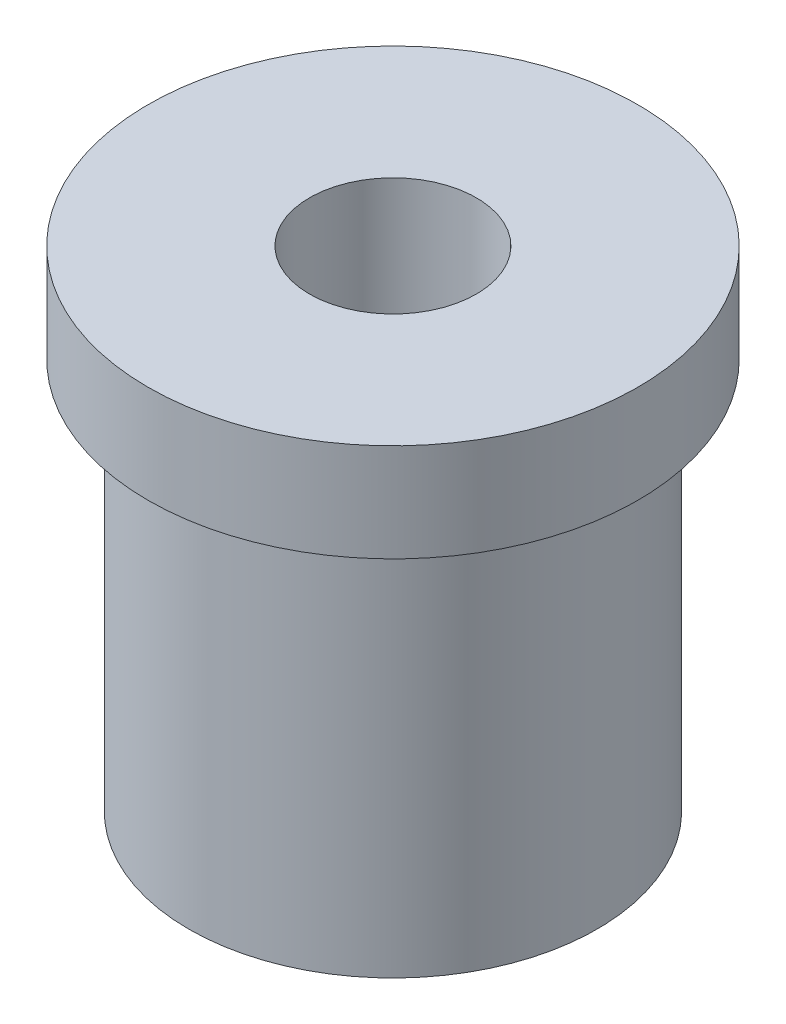
SolidWorks part; units mm, degrees
material "AISI 4130 Steel, annealed at 865C"
ref_plane "Front Plane" through (0, 0, 0) normal (0, 0, 1) x (1, 0, 0)
ref_plane "Top Plane" through (0, 0, 0) normal (0, 1, 0) x (1, 0, 0)
ref_plane "Right Plane" through (0, 0, 0) normal (1, 0, 0) x (0, 0, -1)
sketch "Sketch1" plane through (0, 0, 0) normal (0, 1, 0) x (1, 0, 0)
  circle A0 centre (0, 0) radius 7.9375
  circle A1 centre (0, 0) radius 6.6167
  circle A2 centre (0, 0) radius 2.7051
  dimension "D1" = 15.875
  dimension "D2" = 1.3208
  dimension "D3" = 5.4102
extrude "Boss-Extrude1" add sketch "Sketch1" along normal blind 3.175 contours A0 A1 | A1 A2 region at (-7.713, 0, 0) region at (-6.4296, 0, 0)
extrude "Boss-Extrude2" add sketch "Sketch1<3>" against normal blind 12.7 contours A1 A2 region at (-6.4296, 0, 0)
sketch "Sketch1<3>" plane through (0, 0, 0) normal (0, 1, 0) x (1, 0, 0) same geometry as "Sketch1"
